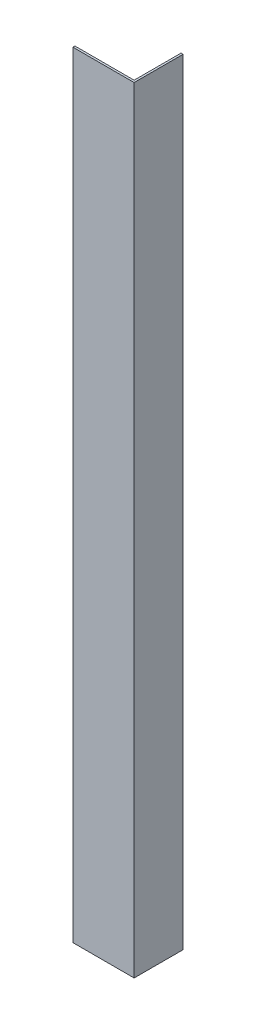
SolidWorks part; units mm, degrees
material "6061-T6 (SS)"
ref_plane "Alzado" through (0, 0, 0) normal (0, 0, 1) x (1, 0, 0)
ref_plane "Planta" through (0, 0, 0) normal (0, 1, 0) x (1, 0, 0)
ref_plane "Vista lateral" through (0, 0, 0) normal (1, 0, 0) x (0, 0, -1)
sketch "Sketch1" plane through (0, 0, 0) normal (0, 1, 0) x (1, 0, 0)
  line L0 (0, 0) -> (15, 0)
  line L1 (15, 0) -> (15, 12)
  line L2 (15, 12) -> (14.5, 12)
  line L3 (14.5, 12) -> (14.5, 0.5)
  line L4 (14.5, 0.5) -> (0, 0.5)
  line L5 (0, 0.5) -> (0, 0)
  dimension "D1" = 15
  dimension "D2" = 12
  dimension "D3" = 0.5
  dimension "D4" = 0.5
extrude "Boss-Extrude1" add sketch "Sketch1" along normal blind 196
sketch "Sketch4" plane through (0, 0, 0) normal (0, 0, 1) x (1, 0, 0)
  line L0 (15, 196) -> (15, 0) construction
  line L1 (0, 196) -> (15, 196)
  line L2 (0, 196) -> (0, 193)
  line L3 (0, 193) -> (15, 193)
  line L4 (15, 196) -> (15, 193)
  line L6 (0, 0) -> (15, 0)
  line L7 (0, 0) -> (0, 3)
  line L8 (0, 3) -> (15, 3)
  line L9 (15, 0) -> (15, 3)
  dimension "D1" = 3
  dimension "D2" = 3
extrude "Cut-Extrude3" cut sketch "Sketch4" against normal up to next
